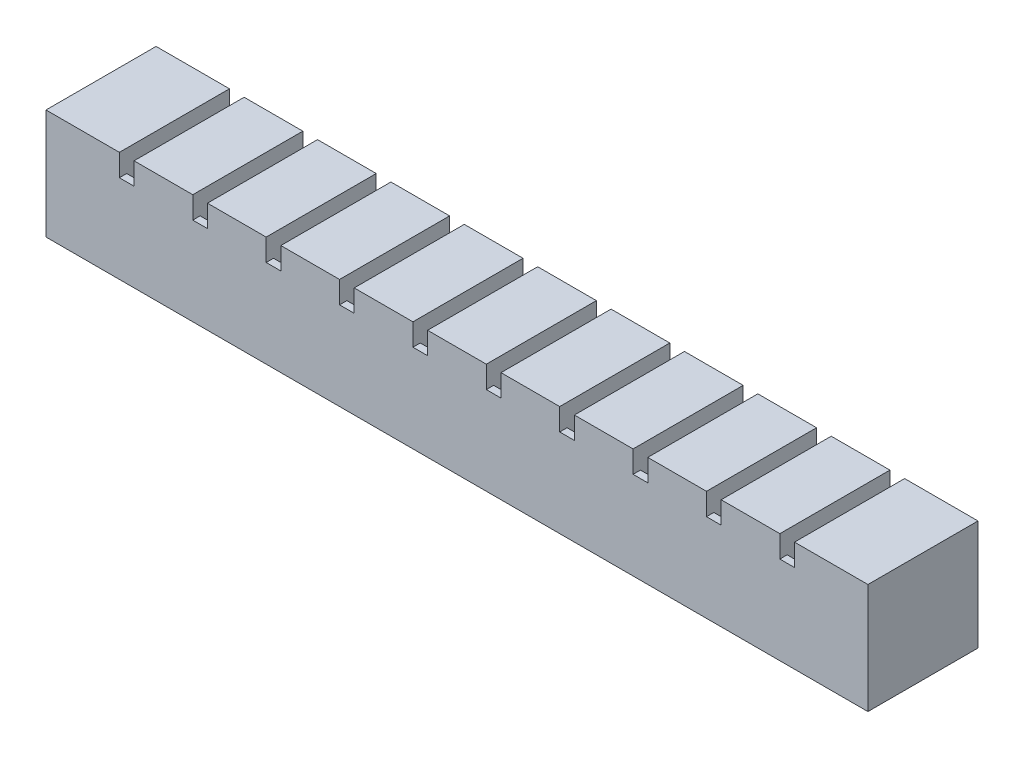
SolidWorks part; units mm, degrees
ref_plane "Front Plane" through (0, 0, 0) normal (0, 0, 1) x (1, 0, 0)
ref_plane "Top Plane" through (0, 0, 0) normal (0, 1, 0) x (1, 0, 0)
ref_plane "Right Plane" through (0, 0, 0) normal (1, 0, 0) x (0, 0, -1)
sketch "Sketch1" plane through (0, 0, 0) normal (0, 0, 1) x (1, 0, 0)
  line L1 (0, 0) -> (8, 0)
  line L2 (0, 0) -> (0, 15)
  line L3 (0, 15) -> (8, 15)
  line L4 (8, 0) -> (8, 15)
  dimension "D1" = 8
  dimension "D2" = 15
extrude "first chamber block" add sketch "Sketch1" along normal blind 15
sketch "Sketch2" plane through (0, 0, 0) normal (0, -1, 0) x (1, 0, 0)
  line L0 (8, 15) -> (8, 0) construction
  line L1 (1, 13) -> (7, 13)
  line L2 (1, 13) -> (1, 2)
  line L3 (1, 2) -> (7, 2)
  line L4 (7, 13) -> (7, 2)
  line L5 (0, 15) -> (0, 0) construction
  line L6 (0, 15) -> (8, 15) construction
  line L7 (0, 0) -> (8, 0) construction
  dimension "D1" = 1
  dimension "D2" = 1
  dimension "D3" = 2
  dimension "D4" = 2
extrude "first chamber cavity" cut sketch "Sketch2" against normal blind 13
sketch "Sketch3" plane through (8, 0, 0) normal (1, 0, 0) x (0, 0, -1)
  line L0 (-15, 0) -> (-15, 15) construction
  line L1 (0, 0) -> (-15, 0)
  line L2 (0, 0) -> (0, 3)
  line L3 (0, 3) -> (-15, 3)
  line L4 (-15, 0) -> (-15, 3)
  dimension "D1" = 3
extrude "chamber spacer" add sketch "Sketch3" along normal blind 2
pattern_linear "pattern chambers" count 11 spacing 10 along (1, 0, 0) of "chamber spacer", "first chamber cavity", "first chamber block"
combine bodies "combine into 1 solid body" operation type add bodies to combine 123 122 121 120 119 118 117 116 115 114 103
sketch "Sketch4" plane through (108, 0, 0) normal (1, 0, 0) x (0, 0, -1)
  line L1 (0, 15) -> (-15, 15)
  line L2 (0, 15) -> (0, 3)
  line L3 (0, 3) -> (-15, 3)
  line L4 (-15, 15) -> (-15, 3)
extrude "thicken end 1" add sketch "Sketch4" along normal up to surface (2 mm away) up to face at (110, 1.5, 7.5)
sketch "Sketch5" plane through (0, 0, 0) normal (-1, 0, 0) x (0, 0, 1)
  line L1 (15, 15) -> (0, 15)
  line L2 (15, 15) -> (15, 0)
  line L3 (15, 0) -> (0, 0)
  line L4 (0, 15) -> (0, 0)
extrude "thicken end 2" add sketch "Sketch5" along normal blind 2
ref_point "center of bottom face"
sketch "Sketch6" plane through (0, 0, 0) normal (0, -1, 0) x (1, 0, 0)
  line L0 (7, 2) -> (7, 13) construction
  line L1 (101, 6.5) -> (7, 6.5)
  line L2 (101, 6.5) -> (101, 8.5)
  line L3 (101, 8.5) -> (7, 8.5)
  line L4 (7, 6.5) -> (7, 8.5)
  line L5 (101, 6.5) -> (7, 8.5) construction
  line L6 (101, 8.5) -> (7, 6.5) construction
  point P0 (54, 7.5)
  dimension "D1" = 2
extrude "central air channel" cut sketch "Sketch6" against normal blind 2
sketch "Sketch7" plane through (0, 0, 0) normal (0, -1, 0) x (1, 0, 0)
  line L0 (0, 14) -> (108, 14)
  line L1 (1, 13) -> (107, 13)
  line L2 (1, 13) -> (1, 2)
  line L3 (1, 2) -> (107, 2)
  line L4 (107, 13) -> (107, 2)
  line L5 (108, 14) -> (108, 1)
  line L6 (0, 1) -> (108, 1)
  line L7 (0, 14) -> (0, 1)
  dimension "D1" = 1
extrude "bonding ridge" add sketch "Sketch7" along normal blind 2
sketch "Sketch9" plane through (0, 0, 0) normal (0, -1, 0) x (1, 0, 0)
  line L0 (11, 8.5) -> (11, 13) construction
  line L1 (11, 13) -> (7, 13) construction
  line L2 (7, 13) -> (7, 8.5) construction
  line L3 (7, 8.5) -> (11, 8.5) construction
  line L4 (7, 6.5) -> (7, 2) construction
  line L5 (7, 2) -> (11, 2) construction
  line L6 (11, 2) -> (11, 6.5) construction
  line L7 (11, 6.5) -> (7, 6.5) construction
  line L8 (11, 8.5) -> (11, 13) construction
  line L9 (11, 13) -> (7, 13) construction
  line L10 (7, 13) -> (7, 8.5) construction
  line L11 (7, 8.5) -> (11, 8.5) construction
  line L12 (7, 6.5) -> (7, 2) construction
  line L13 (7, 2) -> (11, 2) construction
  line L14 (11, 2) -> (11, 6.5) construction
  line L15 (11, 6.5) -> (7, 6.5) construction
  line L16 (10, 9.5) -> (10, 12)
  line L17 (10, 12) -> (8, 12)
  line L18 (8, 12) -> (8, 9.5)
  line L19 (8, 9.5) -> (10, 9.5)
  line L20 (8, 5.5) -> (8, 3)
  line L21 (8, 3) -> (10, 3)
  line L22 (10, 3) -> (10, 5.5)
  line L23 (10, 5.5) -> (8, 5.5)
  dimension "D1" = 1
extrude "bonding bumps" add sketch "Sketch9" along normal blind 2
pattern_linear "pattern bonding bumps" count 10 spacing 10 along (1, 0, 0) of "bonding bumps"
sketch "Skizze1" plane through (0, 0, 0) normal (0, -1, 0) x (1, 0, 0)
  line L4 (-2, 0) -> (110, 0)
  line L5 (110, 0) -> (110, 15)
  line L6 (110, 15) -> (-2, 15)
  line L7 (-2, 15) -> (-2, 0)
  line L8 (-2, 0) -> (110, 0)
  line L9 (110, 0) -> (110, 15)
  line L10 (110, 15) -> (-2, 15)
  line L11 (-2, 15) -> (-2, 0)
  dimension "D1" = 0
extrude "Schnitt-Linear austragen1" cut sketch "Skizze1" along normal through all
sketch "Skizze2" plane through (0, 3, 0) normal (0, 1, 0) x (1, 0, 0)
  line L0 (98, 0) -> (98, -15) construction
  line L1 (100, 0) -> (98, 0)
  line L2 (100, 0) -> (100, -1)
  line L3 (100, -1) -> (98, -1)
  line L4 (98, 0) -> (98, -1)
  line L5 (100, 0) -> (100, -15) construction
  line L6 (98, -15) -> (100, -15)
  line L7 (98, -15) -> (98, -14)
  line L8 (98, -14) -> (100, -14)
  line L9 (100, -15) -> (100, -14)
  dimension "D1" = 1
extrude "Aufsatz-Linear austragen1" add sketch "Skizze2" along normal offset from surface (9 mm away) 3 up to face at (105, 15, 7.5)
pattern_linear "Lineares Muster1" count 10 spacing 10 along (-1, 0, 0) of "Aufsatz-Linear austragen1"
sketch "Skizze3" plane through (0, 0, 2) normal (0, 0, 1) x (1, 0, 0)
  line L0 (104, 0) -> (104, 13) construction
  line L1 (107, 0) -> (101, 0) construction
  line L2 (101, 13) -> (107, 13) construction
  circle A0 centre (104, 6.5) radius 1.25
  dimension "D1" = 2.5
extrude "Schnitt-Linear austragen2" cut sketch "Skizze3" against normal through all
